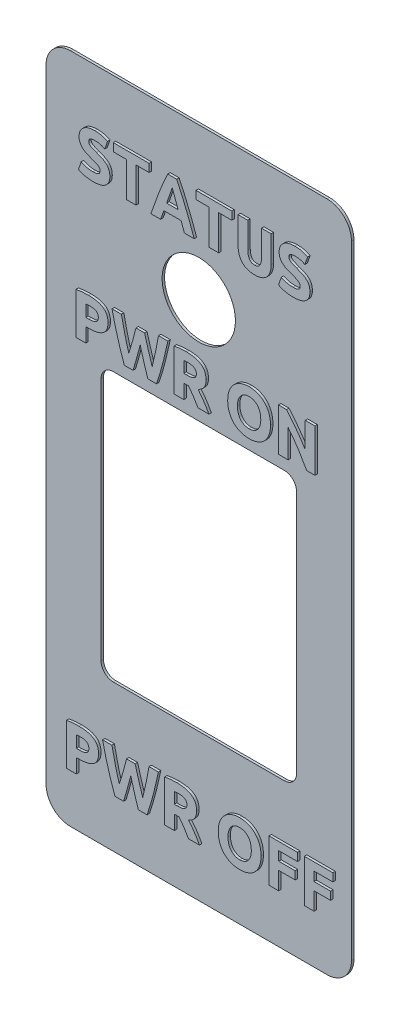
SolidWorks part; units mm, degrees
ref_plane "Front Plane" through (0, 0, 0) normal (0, 0, 1) x (1, 0, 0)
ref_plane "Top Plane" through (0, 0, 0) normal (0, 1, 0) x (1, 0, 0)
ref_plane "Right Plane" through (0, 0, 0) normal (1, 0, 0) x (0, 0, -1)
sketch "Sketch1" plane through (0, 0, 0) normal (0, 0, 1) x (1, 0, 0)
  line L1 (0, 0) -> (25, 0)
  line L2 (0, 0) -> (0, 55)
  line L3 (0, 55) -> (25, 55)
  line L4 (25, 0) -> (25, 55)
  dimension "D1" = 25
  dimension "D2" = 55
extrude "Body" add sketch "Sketch1" along normal blind 0.2
sketch "Sketch3" plane through (0, 0, 0.2) normal (0, 0, 1) x (1, 0, 0)
  line L0 (0, 0) -> (25, 0) construction
  line L1 (4.5, 34) -> (20.5, 34)
  line L2 (4.5, 34) -> (4.5, 12)
  line L3 (4.5, 12) -> (20.5, 12)
  line L4 (20.5, 34) -> (20.5, 12)
  circle A0 centre (12.5, 42.6) radius 3
  point P6 (0, 0)
  point P7 (12.5, 34)
  point P8 (12.8022, 45.0499)
  point P9 (0, 0)
  point P10 (12.5, 12)
  point P13 (12.5, 0)
  dimension "D3" = 6
  dimension "D1" = 16
  dimension "D2" = 22
  dimension "D4" = 8.6
  dimension "D5" = 12
extrude "Cuts" cut sketch "Sketch3" against normal through all
sketch "Sketch2" plane through (0, 0, 0.2) normal (0, 0, 1) x (1, 0, 0)
  text T0 "PWR ON" font "Ubuntu" height 3.5
  text T1 "PWR OFF" font "Ubuntu" height 3.5
  text T2 "STATUS" font "Ubuntu" height 3.5
extrude "Text" add sketch "Sketch2" along normal blind 0.2
fillet "InsideFillet" radius 1 4 edges at (4.5, 12, 0.1) (20.5, 12, 0.1) (20.5, 34, 0.1) (4.5, 34, 0.1)
fillet "OutsideFillet" radius 2 4 edges at (0, 0, 0.1) (25, 0, 0.1) (0, 55, 0.1) (25, 55, 0.1)
